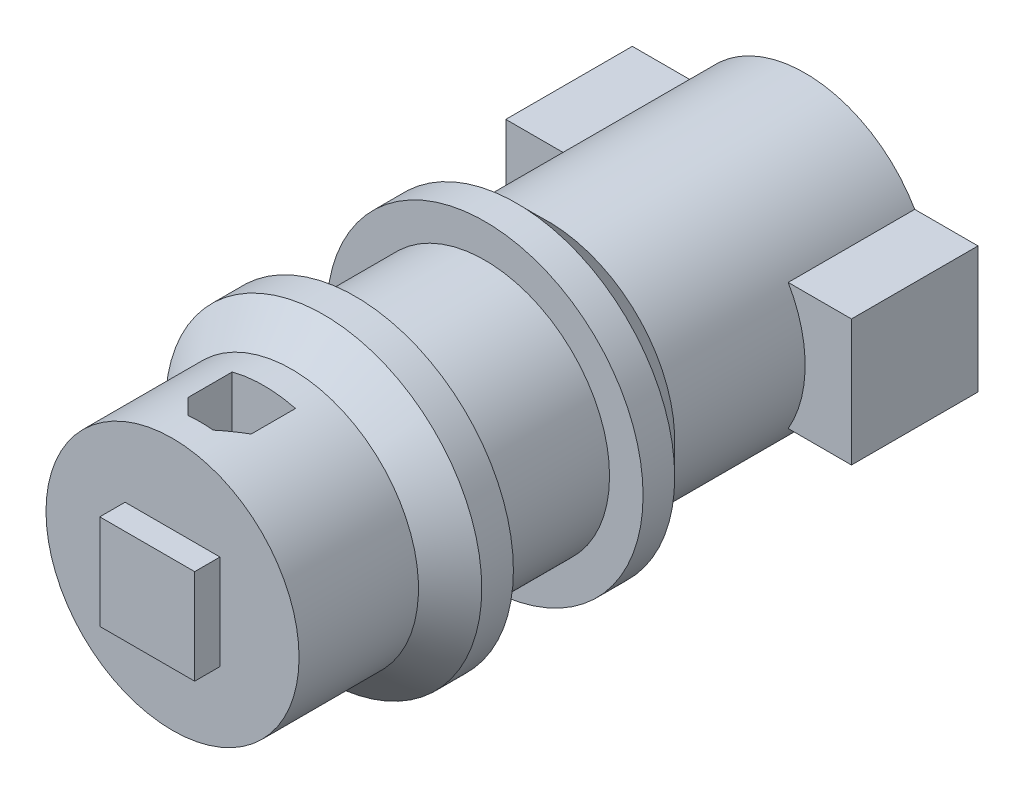
SolidWorks part; units mm, degrees
ref_plane "Front Plane" through (0, 0, 0) normal (0, 0, 1) x (1, 0, 0)
ref_plane "Top Plane" through (0, 0, 0) normal (0, 1, 0) x (1, 0, 0)
ref_plane "Right Plane" through (0, 0, 0) normal (1, 0, 0) x (0, 0, -1)
sketch "Sketch1" plane through (0, 0, 0) normal (0, 0, 1) x (1, 0, 0)
  circle A0 centre (0, 0) radius 10
  dimension "D1" = 20
extrude "Boss-Extrude1" add sketch "Sketch1" along normal blind 50
sketch "Sketch2" plane through (0, 0, 0) normal (0, 0, -1) x (-1, 0, 0)
  line L0 (-8.6603, 5) -> (-13.6603, 5)
  line L1 (-13.6603, 5) -> (-13.6603, -5)
  line L2 (-13.6603, -5) -> (-8.6603, -5)
  line L3 (8.6603, -5) -> (13.6603, -5)
  line L4 (13.6603, -5) -> (13.6603, 5)
  line L5 (13.6603, 5) -> (8.6603, 5)
  circle A0 centre (0, 0) radius 10 construction
  arc A1 (-8.6603, 5) -> (-8.6603, -5) centre (0, 0) ccw
  arc A2 (8.6603, -5) -> (8.6603, 5) centre (0, 0) ccw
  dimension "D1" = 10
  dimension "D2" = 5
extrude "Boss-Extrude2" add sketch "Sketch2" against normal blind 10
sketch "Sketch6" plane through (0, 0, 0) normal (0, 0, -1) x (-1, 0, 0)
  circle A0 centre (0, 0) radius 12.5
  dimension "D1" = 25
extrude "Boss-Extrude5" add sketch "Sketch6" along normal blind 5 from offset 25.31 offset against normal yes
pattern_linear "LPattern1" count 2 spacing 15.25 along (0, 0, 1) of "Boss-Extrude5"
chamfer "Chamfer2" distance 2.5 angle 45 2 edges at (-12.5, 0, 20.31) (-12.5, 0, 40.56)
sketch "Sketch7" plane through (0, 0, 0) normal (0, 1, 0) x (1, 0, 0)
  line L0 (-10, -45.28) -> (10, -45.28) construction
  line L1 (-2.5, -47.78) -> (2.5, -47.78)
  line L2 (-2.5, -47.78) -> (-2.5, -42.78)
  line L3 (-2.5, -42.78) -> (2.5, -42.78)
  line L4 (2.5, -47.78) -> (2.5, -42.78)
  line L5 (-2.5, -47.78) -> (2.5, -42.78) construction
  line L6 (-2.5, -42.78) -> (2.5, -47.78) construction
  line L7 (-10, -40.56) -> (-10, -50) construction
  line L8 (10, -50) -> (10, -40.56) construction
  point P0 (0, -45.28)
  dimension "D1" = 5
extrude "Cut-Extrude1" cut sketch "Sketch7" against normal blind 5 from offset 10
chamfer "Chamfer3" distance 1.5 angle 45 2 edges at (2.5, 7.3412, 47.78) (-2.5, 7.3412, 47.78)
sketch "Sketch8" plane through (0, 0, 50) normal (0, 0, 1) x (1, 0, 0)
  line L1 (-3.75, -3.75) -> (3.75, -3.75)
  line L2 (-3.75, -3.75) -> (-3.75, 3.75)
  line L3 (-3.75, 3.75) -> (3.75, 3.75)
  line L4 (3.75, -3.75) -> (3.75, 3.75)
  line L5 (-3.75, -3.75) -> (3.75, 3.75) construction
  line L6 (-3.75, 3.75) -> (3.75, -3.75) construction
  point P0 (0, 0)
  dimension "D1" = 7.5
  dimension "D2" = 7.5
extrude "Boss-Extrude6" add sketch "Sketch8" along normal blind 2
sketch "Sketch9" [suppressed] plane through (0, 0, 50) normal (0, 0, 1) x (1, 0, 0)
  line L1 (-3.85, -3.85) -> (3.85, -3.85)
  line L2 (-3.85, -3.85) -> (-3.85, 3.85)
  line L3 (-3.85, 3.85) -> (3.85, 3.85)
  line L4 (3.85, -3.85) -> (3.85, 3.85)
  line L5 (-3.85, -3.85) -> (3.85, 3.85) construction
  line L6 (-3.85, 3.85) -> (3.85, -3.85) construction
  point P0 (0, 0)
  dimension "D1" = 7.7
  dimension "D2" = 7.7
extrude "Cut-Extrude2" [suppressed] cut sketch "Sketch9" against normal blind 2
sketch "Sketch10" plane through (0, 0, 25.31) normal (0, 0, 1) x (1, 0, 0)
  circle A0 centre (0, 0) radius 10 construction
  circle A1 centre (0, 0) radius 10
  circle A2 centre (0, 0) radius 9.85
  dimension "D1" = 0.15
extrude "Cut-Extrude3" cut sketch "Sketch10" along normal up to surface (10.25 mm away) up to face at (-10, 0, 35.56)
